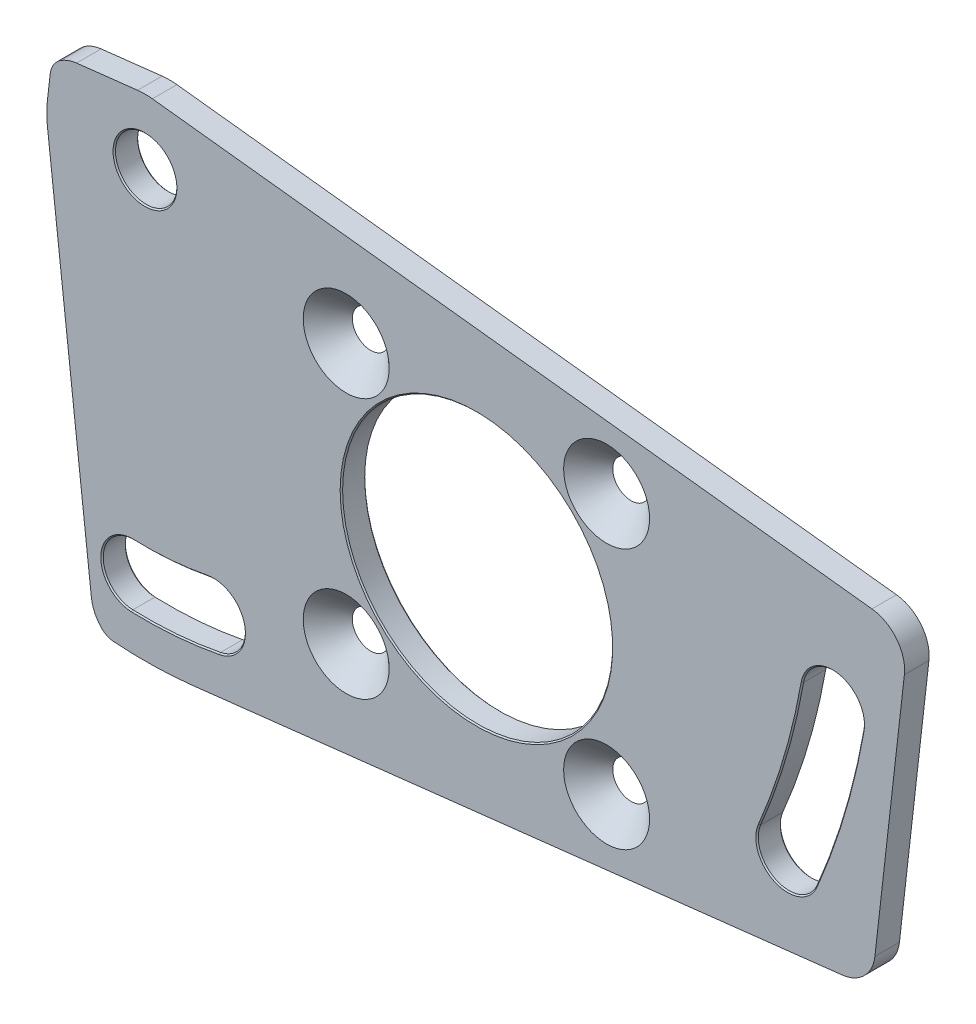
SolidWorks part; units mm, degrees
ref_plane "Płaszczyzna przednia" through (0, 0, 0) normal (0, 0, 1) x (1, 0, 0)
ref_plane "Płaszczyzna górna" through (0, 0, 0) normal (0, 1, 0) x (1, 0, 0)
ref_plane "Płaszczyzna prawa" through (0, 0, 0) normal (1, 0, 0) x (0, 0, -1)
sketch "Szkic1" plane through (0, 0, 0) normal (0, 0, 1) x (1, 0, 0)
  line L0 (25.3611, -7.5593) -> (-27, 14.6667) construction
  line L1 (-32, -20) -> (32, -20)
  line L2 (-35, -17) -> (-35, 17)
  line L3 (-32, 20) -> (32, 20)
  line L4 (35, -17) -> (35, 17)
  line L5 (-35, -20) -> (35, 20) construction
  line L6 (-35, 20) -> (35, -20) construction
  line L7 (-27, 14.6667) -> (29.0188, 4.789) construction
  line L10 (-28, -14.4829) -> (-27, 14.6667) construction
  line L11 (-27, 14.6667) -> (-21.4172, -13.9607) construction
  arc A0 (-32, -20) -> (-35, -17) centre (-32, -17) cw
  arc A1 (32, -20) -> (35, -17) centre (32, -17) ccw
  arc A2 (32, 20) -> (35, 17) centre (32, 17) cw
  arc A3 (-35, 17) -> (-32, 20) centre (-32, 17) cw
  circle A4 centre (0, 0) radius 11
  circle A5 centre (-27, 14.6667) radius 2.5
  arc A6 (25.3611, -7.5593) -> (29.0188, 4.789) centre (-27, 14.6667) ccw construction
  arc A7 (27.6623, -8.5361) -> (31.4808, 4.3549) centre (-27, 14.6667) ccw
  arc A8 (23.0598, -6.5825) -> (26.5568, 5.2232) centre (-27, 14.6667) ccw
  arc A9 (23.0598, -6.5825) -> (27.6623, -8.5361) centre (25.3611, -7.5593) ccw
  arc A10 (31.4808, 4.3549) -> (26.5568, 5.2232) centre (29.0188, 4.789) ccw
  arc A13 (-28, -14.4829) -> (-21.4172, -13.9607) centre (-27, 14.6667) ccw construction
  arc A14 (-28.0857, -16.9814) -> (-20.9386, -16.4145) centre (-27, 14.6667) ccw
  arc A15 (-27.9143, -11.9843) -> (-21.8957, -11.5069) centre (-27, 14.6667) ccw
  arc A16 (-27.9143, -11.9843) -> (-28.0857, -16.9814) centre (-28, -14.4829) ccw
  arc A17 (-20.9386, -16.4145) -> (-21.8957, -11.5069) centre (-21.4172, -13.9607) ccw
  point P0 (0, 0)
  point P25 (27.5405, -1.489)
  point P30 (0, 0)
  point P31 (0, 0)
  point P32 (0, 0)
  point P35 (-24.6938, -14.4087)
  point P36 (27.5405, -1.489)
  dimension "D3" = 3
  dimension "D4" = 5
  dimension "D5" = 22
  dimension "D7" = 2.5
  dimension "D8" = 3
  dimension "D9" = 10
  dimension "D10" = 13
  dimension "D12" = 2.5
  dimension "D11" = 4.5
  dimension "D1" = 70
  dimension "D2" = 40
  dimension "D6" = 13
extrude "Dodanie-wyciągnięcie1" add sketch "Szkic1" along normal blind 2
sketch "Szkic2" plane through (0, 0, 0) normal (0, 0, 1) x (1, 0, 0)
  line L2 (-10.6066, -10.6066) -> (10.6066, -10.6066) construction
  line L3 (-10.6066, -10.6066) -> (-10.6066, 10.6066) construction
  line L4 (-10.6066, 10.6066) -> (10.6066, 10.6066) construction
  line L5 (10.6066, -10.6066) -> (10.6066, 10.6066) construction
  line L6 (-10.6066, -10.6066) -> (10.6066, 10.6066) construction
  line L7 (-10.6066, 10.6066) -> (10.6066, -10.6066) construction
  circle A0 centre (-10.6066, 10.6066) radius 1.5
  circle A1 centre (10.6066, 10.6066) radius 1.5
  circle A2 centre (10.6066, -10.6066) radius 1.5
  circle A3 centre (-10.6066, -10.6066) radius 1.5
  point P11 (0, 0)
  dimension "D1" = 3
  dimension "D2" = 30
extrude "Wytnij-wyciągnięcie2" cut sketch "Szkic2" along normal through all
sketch "Szkic3" plane through (0, 0, 0) normal (0, 0, 1) x (1, 0, 0)
  line L0 (32.4644, -11.109) -> (34.8656, 9.9664)
  line L1 (-34.7231, 17.5512) -> (-34.9486, 15.5723)
  line L2 (32.2245, 13.2867) -> (-26.3962, 19.9657)
  line L9 (-23.0756, -19.7772) -> (29.8233, -13.7501)
  line L11 (-27.6038, 19.9657) -> (-32.5716, 19.3997)
  line L12 (-34.9486, 13.761) -> (-31.3638, -17.7021)
  arc A2 (34.8656, 9.9664) -> (32.2245, 13.2867) centre (31.8849, 10.306) ccw
  arc A4 (-26.3962, 19.9657) -> (-27.6038, 19.9657) centre (-27, 14.6667) ccw
  arc A5 (-33.8699, 18.9324) -> (-34.7231, 17.5512) centre (-32.8292, 17.3354) ccw
  arc A6 (-34.9486, 15.5723) -> (-34.9486, 13.761) centre (-27, 14.6667) ccw
  arc A7 (-29.5516, -19.906) -> (-23.0756, -19.7772) centre (-27, 14.6667) ccw
  arc A8 (-31.3638, -17.7021) -> (-30.5562, -19.4307) centre (-28.3831, -17.3625) ccw
  arc A11 (-32.5716, 19.3997) -> (-33.8699, 18.9324) centre (-32.232, 16.419) ccw
  arc A12 (29.8233, -13.7501) -> (32.4644, -11.109) centre (29.4836, -10.7694) ccw
  arc A13 (-30.5562, -19.4307) -> (-29.5516, -19.906) centre (-29.438, -18.3665) ccw
  point P0 (-27, 14.6667)
  point P1 (-27, 14.6667)
  dimension "D1" = 3
extrude "Wytnij-wyciągnięcie3" cut sketch "Szkic3" along normal through all flip side to cut
chamfer "Sfazowanie1" distance 2 angle 45 4 edges at (-9.1066, -10.6066, 2) (12.1066, -10.6066, 2) (12.1066, 10.6066, 2) (-9.1066, 10.6066, 2)
chamfer "Sfazowanie2" distance 0.1 angle 45 20 edges at (29.9376, -2.199, 2) (29.4529, 7.2511, 2) (24.3842, -9.8605, 2) (25.1435, -0.7789, 2) (29.9376, -2.199, 0) (29.4529, 7.2511, 0) (24.3842, -9.8605, 0) (25.1435, -0.7789, 0) (-24.5, 14.6667, 0) (-24.5, 14.6667, 2) (11, 0, 0) (11, 0, 2) (-18.9634, -13.4822, 2) (-24.8914, -11.9165, 2) (-24.4961, -16.9009, 2) (-30.4985, -14.3971, 2) (-18.9634, -13.4822, 0) (-24.8914, -11.9165, 0) (-24.4961, -16.9009, 0) (-30.4985, -14.3971, 0)
